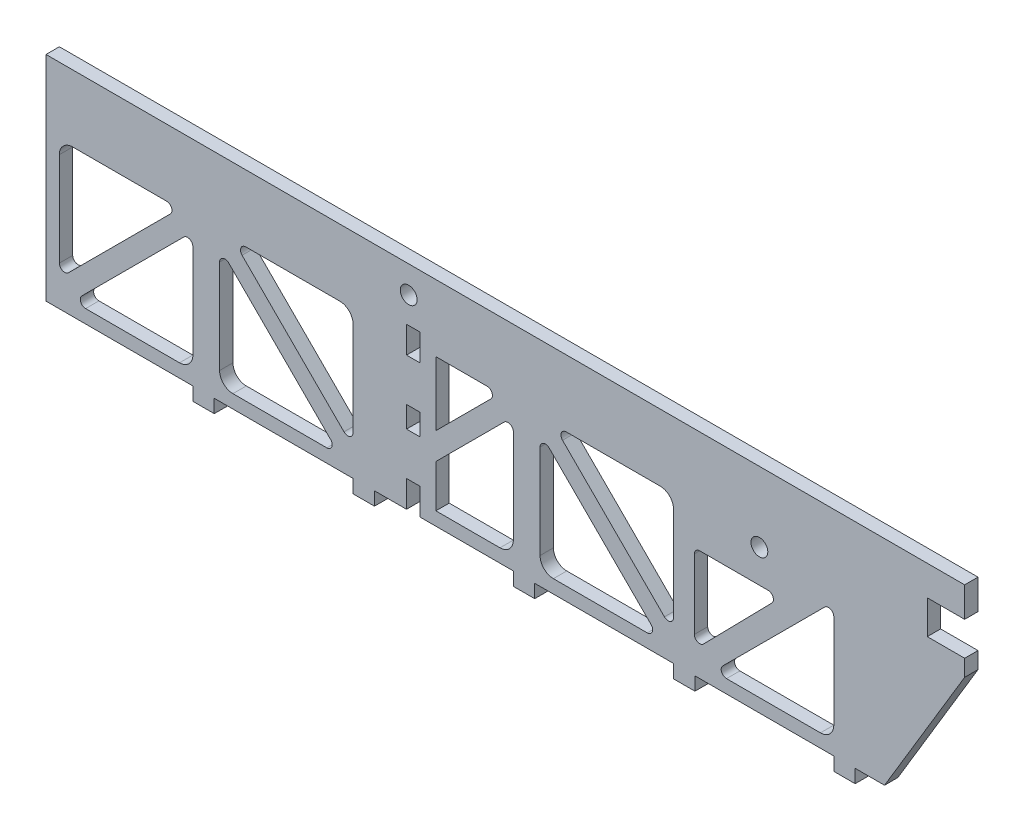
SolidWorks part; units mm, degrees
material "Pine"
ref_plane "Front Plane" through (0, 0, 0) normal (0, 0, 1) x (1, 0, 0)
ref_plane "Top Plane" through (0, 0, 0) normal (0, 1, 0) x (1, 0, 0)
ref_plane "Right Plane" through (0, 0, 0) normal (1, 0, 0) x (0, 0, -1)
sketch "Model" plane through (0, 0, 0) normal (0, 0, 1) x (1, 0, 0)
  line L0 (312.6855, 15.1239) -> (345.2281, 48.2988)
  line L1 (343.4149, 52.6175) -> (310.8722, 52.6175)
  line L2 (308.3322, 50.0775) -> (308.3322, 16.9026)
  line L8 (171.2321, 6.35) -> (215.9, 6.35)
  line L9 (217.9139, 59.1639) -> (169.4361, 10.6861)
  line L10 (222.25, 57.3679) -> (222.25, 12.7)
  line L11 (234.95, 57.3679) -> (234.95, 12.7)
  line L12 (239.2861, 59.1639) -> (287.7639, 10.6861)
  line L13 (241.3, 6.35) -> (285.9679, 6.35)
  line L14 (294.1139, 17.0361) -> (245.6361, 65.5139)
  line L15 (247.4321, 69.85) -> (292.1, 69.85)
  line L16 (298.45, 63.5) -> (298.45, 18.8321)
  line L17 (323.6321, 6.35) -> (368.3, 6.35)
  line L18 (370.3139, 59.1639) -> (321.8361, 10.6861)
  line L19 (374.65, 57.3679) -> (374.65, 12.7)
  line L20 (18.8321, 6.35) -> (63.5, 6.35)
  line L21 (17.0361, 10.6861) -> (65.5139, 59.1639)
  line L22 (69.85, 57.3679) -> (69.85, 12.7)
  line L23 (82.55, 57.3679) -> (82.55, 12.7)
  line L24 (86.8861, 59.1639) -> (135.3639, 10.6861)
  line L25 (88.9, 6.35) -> (133.5679, 6.35)
  line L26 (93.2361, 65.5139) -> (141.7139, 17.0361)
  line L27 (95.0321, 69.85) -> (139.7, 69.85)
  line L28 (146.05, 63.5) -> (146.05, 18.8321)
  line L29 (163.0861, 17.0361) -> (211.5639, 65.5139)
  line L30 (158.75, 63.5) -> (158.75, 18.8321)
  line L31 (165.1, 69.85) -> (209.7679, 69.85)
  line L35 (419.1, 87.376) -> (419.1, 71.374)
  line L36 (436.88, 87.376) -> (419.1, 87.376)
  line L37 (436.88, 87.376) -> (436.88, 95.25)
  line L38 (0, 95.25) -> (436.88, 95.25)
  line L39 (0, 0) -> (0, 95.25)
  line L40 (0, 0) -> (398.78, 0)
  line L41 (436.88, 63.5) -> (398.78, 0)
  line L42 (436.88, 63.5) -> (436.88, 71.374)
  line L43 (419.1, 71.374) -> (436.88, 71.374)
  line L44 (6.35, 63.5) -> (6.35, 18.8321)
  line L45 (12.7, 69.85) -> (57.3679, 69.85)
  line L46 (59.1639, 65.5139) -> (10.6861, 17.0361)
  arc A0 (215.9, 6.35) -> (222.25, 12.7) centre (215.9, 12.7) ccw
  arc A1 (169.4361, 10.6861) -> (171.2321, 6.35) centre (171.2321, 8.89) ccw
  arc A2 (222.25, 57.3679) -> (217.9139, 59.1639) centre (219.71, 57.3679) ccw
  arc A3 (239.2861, 59.1639) -> (234.95, 57.3679) centre (237.49, 57.3679) ccw
  arc A4 (285.9679, 6.35) -> (287.7639, 10.6861) centre (285.9679, 8.89) ccw
  arc A5 (234.95, 12.7) -> (241.3, 6.35) centre (241.3, 12.7) ccw
  arc A6 (247.4321, 69.85) -> (245.6361, 65.5139) centre (247.4321, 67.31) ccw
  arc A7 (298.45, 63.5) -> (292.1, 69.85) centre (292.1, 63.5) ccw
  arc A8 (294.1139, 17.0361) -> (298.45, 18.8321) centre (295.91, 18.8321) ccw
  arc A9 (321.8361, 10.6861) -> (323.6321, 6.35) centre (323.6321, 8.89) ccw
  arc A10 (374.65, 57.3679) -> (370.3139, 59.1639) centre (372.11, 57.3679) ccw
  arc A11 (368.3, 6.35) -> (374.65, 12.7) centre (368.3, 12.7) ccw
  arc A12 (63.5, 6.35) -> (69.85, 12.7) centre (63.5, 12.7) ccw
  arc A13 (17.0361, 10.6861) -> (18.8321, 6.35) centre (18.8321, 8.89) ccw
  arc A14 (69.85, 57.3679) -> (65.5139, 59.1639) centre (67.31, 57.3679) ccw
  arc A15 (86.8861, 59.1639) -> (82.55, 57.3679) centre (85.09, 57.3679) ccw
  arc A16 (133.5679, 6.35) -> (135.3639, 10.6861) centre (133.5679, 8.89) ccw
  arc A17 (82.55, 12.7) -> (88.9, 6.35) centre (88.9, 12.7) ccw
  arc A18 (95.0321, 69.85) -> (93.2361, 65.5139) centre (95.0321, 67.31) ccw
  arc A19 (146.05, 63.5) -> (139.7, 69.85) centre (139.7, 63.5) ccw
  arc A20 (141.7139, 17.0361) -> (146.05, 18.8321) centre (143.51, 18.8321) ccw
  arc A21 (158.75, 18.8321) -> (163.0861, 17.0361) centre (161.29, 18.8321) ccw
  arc A22 (165.1, 69.85) -> (158.75, 63.5) centre (165.1, 63.5) ccw
  arc A23 (211.5639, 65.5139) -> (209.7679, 69.85) centre (209.7679, 67.31) ccw
  arc A24 (345.2281, 48.2988) -> (343.4149, 52.6175) centre (343.4149, 50.0775) ccw
  arc A25 (310.8722, 52.6175) -> (308.3322, 50.0775) centre (310.8722, 50.0775) ccw
  arc A26 (312.6855, 15.1239) -> (308.3322, 16.9026) centre (310.8722, 16.9026) cw
  arc A27 (6.35, 18.8321) -> (10.6861, 17.0361) centre (8.89, 18.8321) ccw
  arc A28 (12.7, 69.85) -> (6.35, 63.5) centre (12.7, 63.5) ccw
  arc A29 (59.1639, 65.5139) -> (57.3679, 69.85) centre (57.3679, 67.31) ccw
  circle A30 centre (172.4917, 88.8013) radius 4
  circle A31 centre (339.2605, 68.3246) radius 4
  circle A32 centre (172.4917, 88.8013) radius 168.021 construction
  dimension "D2" = 6.4487
  dimension "D3" = 172.4917
  dimension "D4" = 8
  dimension "D5" = 20.4767
  dimension "D6" = 8
  dimension "D8" = 2.54
  dimension "D1" = 95.25
  dimension "D7" = 166.7688
extrude "Boss-Extrude2" add sketch "Model" along normal blind 6.35
sketch "Sketch1" plane through (0, 0, 6.35) normal (0, 0, 1) x (1, 0, 0)
  line L0 (69.85, 12.7) -> (69.85, 0) construction
  line L1 (146.05, 95.25) -> (146.05, 0) construction
  line L2 (146.05, 18.8321) -> (146.05, 63.5) construction
  line L3 (0, 0) -> (398.78, 0) construction
  line L4 (222.25, 95.25) -> (222.25, 0) construction
  line L5 (222.25, 12.7) -> (222.25, 57.3679) construction
  line L6 (298.45, 18.8321) -> (298.45, 0) construction
  line L7 (146.05, 0) -> (156.21, 0)
  line L8 (69.85, 0) -> (80.01, 0)
  line L9 (69.85, 0) -> (69.85, -6.35)
  line L10 (69.85, -6.35) -> (80.01, -6.35)
  line L11 (80.01, 0) -> (80.01, -6.35)
  line L16 (222.25, 0) -> (232.41, 0)
  line L17 (222.25, 0) -> (222.25, -6.35)
  line L18 (222.25, -6.35) -> (232.41, -6.35)
  line L19 (232.41, 0) -> (232.41, -6.35)
  line L20 (146.05, 0) -> (146.05, -6.35)
  line L21 (146.05, -6.35) -> (156.21, -6.35)
  line L22 (156.21, 0) -> (156.21, -6.35)
  line L24 (374.65, 12.7) -> (374.65, 0) construction
  line L25 (374.65, 12.7) -> (374.65, 57.3679) construction
  line L27 (298.45, 0) -> (308.61, 0)
  line L28 (298.45, 0) -> (298.45, -6.35)
  line L29 (298.45, -6.35) -> (308.61, -6.35)
  line L30 (308.61, 0) -> (308.61, -6.35)
  line L31 (374.65, 0) -> (384.81, 0)
  line L32 (374.65, 0) -> (374.65, -6.35)
  line L33 (374.65, -6.35) -> (384.81, -6.35)
  line L34 (384.81, 0) -> (384.81, -6.35)
  line L39 (0, 101.6) -> (436.88, 101.6)
  line L53 (0, 95.25) -> (0, 101.6)
  line L55 (436.88, 95.25) -> (436.88, 101.6)
  line L56 (436.88, 95.25) -> (0, 95.25) construction
  line L57 (0, 95.25) -> (436.88, 95.25)
  arc A0 (368.3, 6.35) -> (374.65, 12.7) centre (368.3, 12.7) ccw construction
  dimension "D1" = 10.16
  dimension "D2" = 6.35
  dimension "D3" = 10.16
  dimension "D4" = 6.35
  dimension "D5" = 10.16
  dimension "D6" = 10.16
  dimension "D7" = 10.16
  dimension "D13" = 6.35
extrude "Boss-Extrude3" add sketch "Sketch1" against normal up to surface (6.35 mm away) up to face at (321.5295, 39.2174, 0)
sketch "Sketch2" plane through (0, 0, 6.35) normal (0, 0, 1) x (1, 0, 0)
  line L0 (156.21, 0) -> (222.25, 0) construction
  line L1 (165.1, 79.7539) -> (185.42, 79.7539)
  line L2 (165.1, 79.7539) -> (165.1, 0)
  line L3 (165.1, 0) -> (185.42, 0)
  line L4 (185.42, 79.7539) -> (185.42, 0)
  line L5 (158.75, 63.5) -> (158.75, 18.8321) construction
  line L7 (171.45, 0) -> (177.8, 0)
  line L8 (171.45, 0) -> (171.45, 12.7)
  line L9 (171.45, 12.7) -> (177.8, 12.7)
  line L10 (177.8, 0) -> (177.8, 12.7)
  line L11 (171.45, 33.02) -> (177.8, 33.02)
  line L12 (171.45, 33.02) -> (171.45, 43.18)
  line L13 (171.45, 43.18) -> (177.8, 43.18)
  line L14 (177.8, 33.02) -> (177.8, 43.18)
  line L15 (171.45, 63.5) -> (177.8, 63.5)
  line L16 (171.45, 63.5) -> (171.45, 76.2)
  line L17 (171.45, 76.2) -> (177.8, 76.2)
  line L18 (177.8, 63.5) -> (177.8, 76.2)
  line L19 (146.05, -6.35) -> (156.21, -6.35) construction
  dimension "D1" = 6.35
  dimension "D2" = 20.32
  dimension "D3" = 6.35
  dimension "D4" = 6.35
  dimension "D5" = 6.35
  dimension "D6" = 12.7
  dimension "D7" = 20.32
  dimension "D8" = 20.32
  dimension "D9" = 10.16
  dimension "D10" = 12.7
extrude "Boss-Extrude4" add sketch "Sketch2" against normal up to surface (6.35 mm away) contours L10 L3 L4 L1 L2 L8 L9 L18 L15 L16 L17 L14 L11 L12 L13 region at (175.26, 78.9309, 6.35) up to face at (321.5295, 39.2174, 0)
extrude "Cut-Extrude1" cut sketch "Sketch2<3>" along direction (0, 0, 1) on the side against the normal up to surface (6.35 mm away) from surface contours L3 L10 L9 L8 | L15 L18 L17 L16 region at (174.625, 6.35, 6.35) region at (174.625, 69.85, 6.35) up to face at (174.625, 9.525, 0) starting at face at (174.625, 9.525, 6.35)
sketch "Sketch2<3>" plane through (0, 0, 6.35) normal (0, 0, 1) x (1, 0, 0) same geometry as "Sketch2"
sketch "Sketch3" plane through (0, 0, 6.35) normal (0, 0, 1) x (1, 0, 0)
  line L1 (154.8502, 72.8404) -> (168.7325, 72.8404)
  line L2 (154.8502, 72.8404) -> (154.8502, 13.7288)
  line L3 (154.8502, 13.7288) -> (168.7325, 13.7288)
  line L4 (168.7325, 72.8404) -> (168.7325, 13.7288)
extrude "Boss-Extrude5" add sketch "Sketch3" against normal up to surface (6.35 mm away) up to face at (174.625, 69.85, 0)
